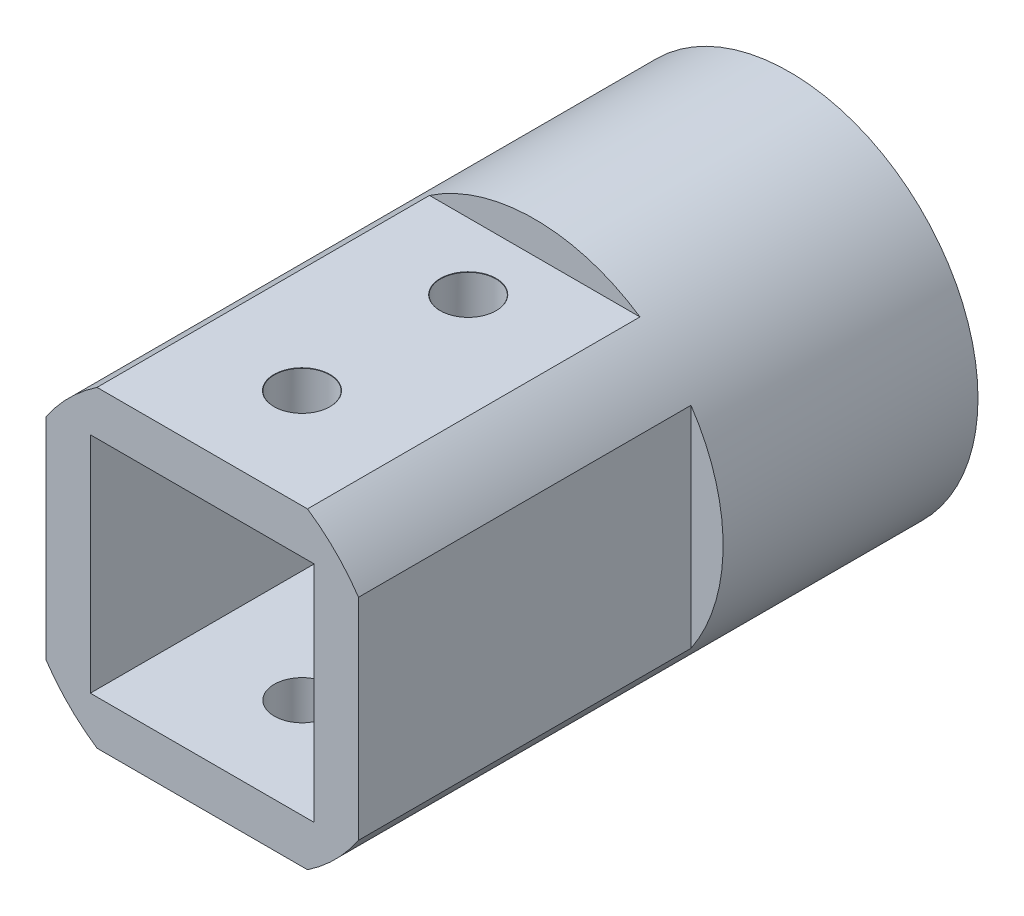
SolidWorks part; units mm, degrees
ref_plane "前视基准面" through (0, 0, 0) normal (0, 0, 1) x (1, 0, 0)
ref_plane "上视基准面" through (0, 0, 0) normal (0, 1, 0) x (1, 0, 0)
ref_plane "右视基准面" through (0, 0, 0) normal (1, 0, 0) x (0, 0, -1)
sketch "草图1" plane through (0, 0, 0) normal (0, 0, 1) x (1, 0, 0)
  circle A0 centre (0, 0) radius 17
  dimension "D1" = 34
extrude "凸台-拉伸1" add sketch "草图1" along normal blind 3
sketch "草图2" plane through (0, 0, 3) normal (0, 0, 1) x (1, 0, 0)
  circle A0 centre (0, 0) radius 17 construction
  circle A1 centre (0, 0) radius 17
  circle A2 centre (0, 0) radius 15
  dimension "D1" = 30
extrude "凸台-拉伸2" add sketch "草图2" along normal blind 10
sketch "草图3" plane through (0, 0, 3) normal (0, 0, 1) x (1, 0, 0)
  circle A0 centre (0, 0) radius 5
  dimension "D1" = 10
extrude "切除-拉伸1" cut sketch "草图3" against normal through all
sketch "草图4" plane through (0, 0, 13) normal (0, 0, 1) x (1, 0, 0)
  line L0 (0, 17) -> (0, -17) construction
  line L1 (-17, 0) -> (0, 0) construction
  line L2 (-4.4431, 10.1) -> (4.4431, 10.1)
  line L7 (10.1, 4.4431) -> (10.1, -4.4431)
  line L8 (-10.1, 4.4431) -> (-10.1, -4.4431)
  line L9 (-4.4431, 10.1) -> (-10.1, 4.4431)
  line L10 (4.4431, 10.1) -> (10.1, 4.4431)
  line L11 (-4.4431, -10.1) -> (-10.1, -4.4431)
  line L12 (-4.4431, -10.1) -> (4.4431, -10.1)
  line L13 (4.4431, -10.1) -> (10.1, -4.4431)
  circle A0 centre (0, 0) radius 17
  point P3 (-10.3021, 0)
  point P9 (0, 10.6167)
  point P17 (0, 10.1)
  point P18 (-10.1, 0)
  point P21 (10.1, 0)
  dimension "D1" = 10.1
  dimension "D2" = 10.1
  dimension "D3" = 8
  dimension "D4" = 135
extrude "凸台-拉伸3" add sketch "草图4" along normal blind 10
sketch "草图5" plane through (0, 0, 23) normal (0, 0, 1) x (1, 0, 0)
  line L2 (-9.4968, 14.1) -> (9.4968, 14.1)
  line L4 (-14.1, 9.4968) -> (-14.1, -9.4968)
  line L6 (0, 0) -> (10.1, 10.1) construction
  line L7 (14.1, -9.4968) -> (14.1, 9.4968)
  line L8 (9.4968, -14.1) -> (-9.4968, -14.1)
  line L11 (-10.1, 10.1) -> (-10.1, -10.1)
  line L12 (-10.1, -10.1) -> (10.1, -10.1)
  line L13 (10.1, -10.1) -> (10.1, 10.1)
  line L14 (10.1, 10.1) -> (-10.1, 10.1)
  circle A1 centre (0, 0) radius 17 construction
  arc A2 (-14.1, -9.4968) -> (-9.4968, -14.1) centre (0, 0) ccw
  arc A3 (-9.4968, 14.1) -> (-14.1, 9.4968) centre (0, 0) ccw
  arc A4 (14.1404, 9.4366) -> (9.4366, 14.1404) centre (0, 0) ccw
  arc A5 (14.1, -9.4968) -> (9.4968, -14.1) centre (0, 0) cw
  circle M7 centre (0, 0) radius 17
  dimension "D1" = 4
  dimension "D2" = 4
  dimension "D3" = 20.2
  dimension "D4" = 20.2
extrude "凸台-拉伸4" add sketch "草图5" along normal blind 30 contours L6 A4 L2 L4 M7 | L6 A2 L8 L7 M7 region at (0, 13.7012, 23)
hole_wizard "Ø5.0mm 暗销孔1" positions "草图6" profile "草图7" hole size "Ø5.0" standard "ISO" end condition through all
sketch "草图6" plane through (0, 14.1, 0) normal (0, 1, 0) x (1, 0, 0)
  line L2 (-9.4968, -23) -> (9.4968, -23) construction
  point P0 (0, -29)
  point P2 (0, -44)
  point P9 (0, 0)
  point P16 (-10.7347, -38.493)
  dimension "D1" = 6
  dimension "D2" = 15
sketch "草图7" plane through (0, 14.1, 29) normal (1, 0, 0) x (0, 0, 1)
  line L0 (0, 0) -> (0, 31.1)
  line L1 (0, 31.1) -> (2.5, 31.1)
  line L2 (2.5, 31.1) -> (2.5, 0.025)
  line L3 (2.5, 0.025) -> (2.525, 0)
  line L5 (2.525, 0) -> (0, 0)
  line L6 (-2.5, 0.025) -> (-2.525, 0) construction
  line L11 (0, -6.35) -> (0, 107.95) construction
  dimension "通孔孔直径" = 5
  dimension "通孔孔深度" = 31.1
  dimension "近端锥形沉头孔直径" = 5.05
  dimension "近端锥形沉头孔角度" = 90
hole_wizard "Ø2.5mm 暗销孔1" positions "草图9" profile "草图10" hole size "Ø2.5" standard "ISO" end condition through all
sketch "草图9" plane through (0, 0, 3) normal (0, 0, 1) x (1, 0, 0)
  point P0 (0, 8)
  point P11 (8, 0)
  point P12 (0, -8)
  point P13 (-8, 0)
  dimension "D1" = 8
  dimension "D2" = 4
sketch "草图10" plane through (0, 8, 3) normal (1, 0, 0) x (0, -1, 0)
  line L0 (0, 0) -> (0, 3)
  line L1 (0, 3) -> (1.25, 3)
  line L2 (1.25, 3) -> (1.25, 0.025)
  line L3 (1.25, 0.025) -> (1.275, 0)
  line L5 (1.275, 0) -> (0, 0)
  line L6 (-1.25, 0.025) -> (-1.275, 0) construction
  line L11 (0, -6.35) -> (0, 107.95) construction
  dimension "通孔孔直径" = 2.5
  dimension "通孔孔深度" = 3
  dimension "近端锥形沉头孔直径" = 2.55
  dimension "近端锥形沉头孔角度" = 90
